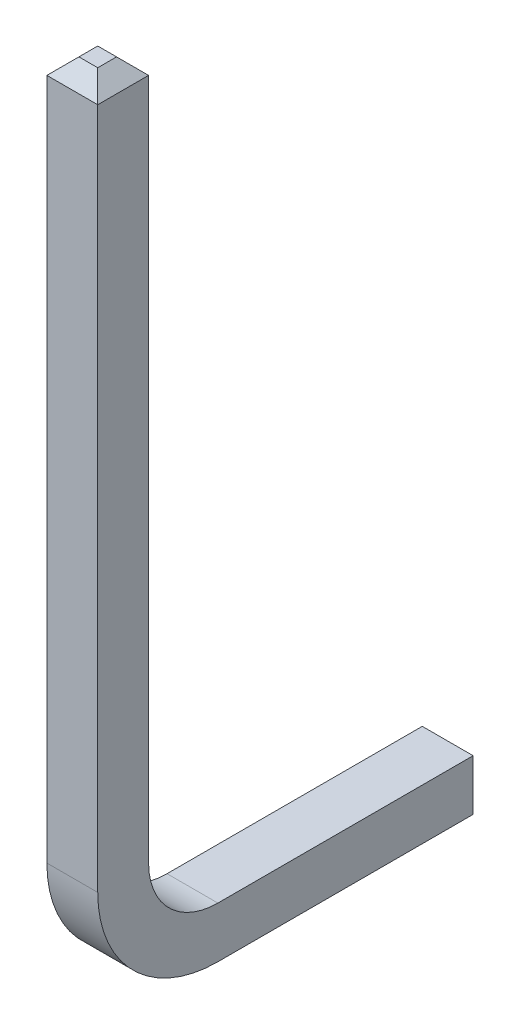
SolidWorks part; units mm, degrees
material "1060 Alloy"
ref_plane "Front Plane" through (0, 0, 0) normal (0, 0, 1) x (1, 0, 0)
ref_plane "Top Plane" through (0, 0, 0) normal (0, 1, 0) x (1, 0, 0)
ref_plane "Right Plane" through (0, 0, 0) normal (1, 0, 0) x (0, 0, -1)
sketch "Sketch1" plane through (0, 0, 0) normal (1, 0, 0) x (0, 0, -1)
  line L0 (0.635, 1.5) -> (0.635, 10.2175)
  line L1 (0.635, 10.2175) -> (0, 10.2175)
  line L2 (0, 10.2175) -> (0, 1.5)
  line L3 (1.5, 0) -> (4.887, 0)
  line L4 (4.887, 0) -> (4.887, 0.635)
  line L5 (4.887, 0.635) -> (1.5, 0.635)
  arc A0 (0, 1.5) -> (1.5, 0) centre (1.5, 1.5) ccw
  arc A1 (1.5, 0.635) -> (0.635, 1.5) centre (1.5, 1.5) cw
  point P9 (0, 0)
  dimension "D4" = 1.5
  dimension "D1" = 10.2175
  dimension "D2" = 0.635
  dimension "D3" = 4.887
extrude "Boss-Extrude1" add sketch "Sketch1" against normal blind 0.635
chamfer "Chamfer1" distance 0.2 angle 45 8 edges at (0, 10.2175, -0.3175) (-0.3175, 10.2175, -0.635) (-0.3175, 10.2175, 0) (-0.635, 10.2175, -0.3175) (-0.3175, 0.635, -4.887) (-0.635, 0.3175, -4.887) (-0.3175, 0, -4.887) (0, 0.3175, -4.887)
sketch "Sketch2" plane through (0, 10.2175, 0) normal (0, 1, 0) x (1, 0, 0)
  line L0 (-0.435, 0.3175) -> (-0.2, 0.3175) construction
  line L1 (-0.435, 0.435) -> (-0.435, 0.2) construction
  line L2 (-0.2, 0.2) -> (-0.2, 0.435) construction
  line L3 (-0.3175, 0.3175) -> (-0.3175, 0.435) construction
  line L4 (-0.2, 0.435) -> (-0.435, 0.435) construction
sketch "Sketch3" plane through (0, 0, -4.887) normal (0, 0, -1) x (-1, 0, 0)
  line L0 (0.435, 0.3175) -> (0.2, 0.3175) construction
  line L1 (0.435, 0.2) -> (0.435, 0.435) construction
  line L2 (0.2, 0.435) -> (0.2, 0.2) construction
  line L3 (0.3175, 0.3175) -> (0.3175, 0.435) construction
  line L4 (0.435, 0.435) -> (0.2, 0.435) construction
ref_axis "Axis1" through (-0.3175, 0.3175, -4.887) along (0, 0, 1)
ref_axis "Axis2" through (-0.3175, 10.2175, -0.3175) along (0, -1, 0)
equation "\"D1@Boss-Extrude1\"=\"D2@Sketch1\""
